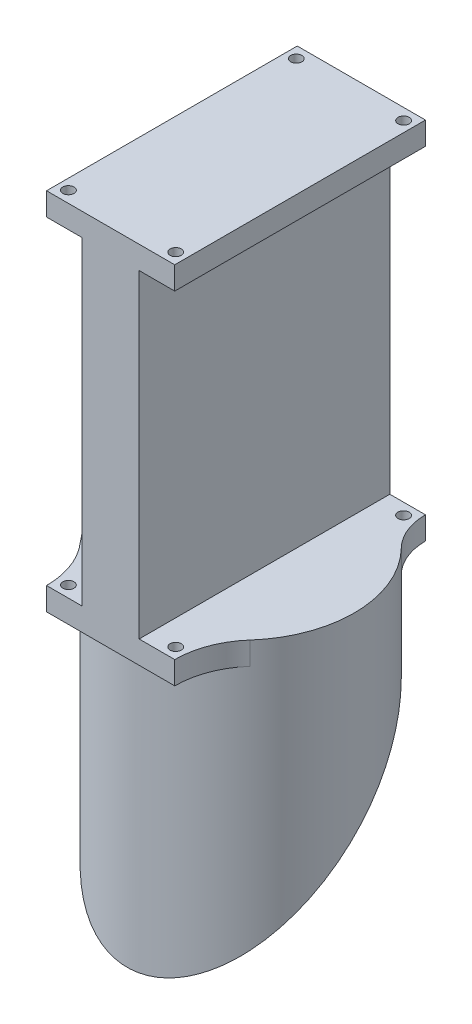
SolidWorks part; units mm, degrees
ref_plane "Front Plane" through (0, 0, 0) normal (0, 0, 1) x (1, 0, 0)
ref_plane "Top Plane" through (0, 0, 0) normal (0, 1, 0) x (1, 0, 0)
ref_plane "Right Plane" through (0, 0, 0) normal (1, 0, 0) x (0, 0, -1)
sketch "Sketch2" plane through (0, 0, 0) normal (1, 0, 0) x (0, 0, -1)
  line L0 (1.0414, 1055.2611) -> (1.0414, 991.9416) construction
  line L1 (1.0414, 1055.2611) -> (-24.2683, 1055.2611)
  line L2 (-24.2683, 1055.2611) -> (-24.2683, 991.9416)
  line L3 (-24.2683, 991.9416) -> (1.0414, 991.9416)
  line L4 (1.0414, 1055.2611) -> (1.0414, 991.9416)
revolve "Revolve1" add sketch "Sketch2" angle 360 about L0
sketch "Sketch3" plane through (0, 0, 0) normal (1, 0, 0) x (0, 0, -1)
  line L0 (-24.2683, 991.9416) -> (26.3511, 1042.5611)
  line L1 (26.3511, 1042.5611) -> (26.3511, 991.9416)
  line L2 (26.3511, 991.9416) -> (-24.2683, 991.9416)
extrude "Cut-Extrude1" cut sketch "Sketch3" against normal through all both and the other way through all
shell "Shell1" thickness 3.175 removed face at (0, 1042.5611, -26.3511)
sketch "Sketch4" plane through (0, 1055.2611, 0) normal (0, 1, 0) x (1, 0, 0)
  line L12 (14.2875, -27.94) -> (14.2875, 27.94) construction
  line L13 (14.2875, -27.94) -> (-14.2875, -27.94)
  line L14 (-14.2875, -27.94) -> (-14.2875, 27.94) construction
  line L15 (14.2875, 27.94) -> (-14.2875, 27.94)
  line L16 (14.2875, -27.94) -> (-14.2875, 27.94) construction
  line L17 (-14.2875, -27.94) -> (14.2875, 27.94) construction
  arc A0 (14.2875, 27.94) -> (18.0321, 18.8016) centre (27.3104, 27.94) ccw
  circle A1 centre (0, 1.0414) radius 25.3097
  arc A2 (-18.0321, 18.8016) -> (-18.9132, -15.7775) centre (0, 1.0414) ccw
  arc A3 (18.9132, -15.7775) -> (14.2875, -27.94) centre (32.5901, -27.94) ccw
  arc A4 (-14.2875, -27.94) -> (-18.9132, -15.7775) centre (-32.5901, -27.94) ccw
  arc A5 (-14.2875, 27.94) -> (-18.0321, 18.8016) centre (-27.3104, 27.94) cw
  arc A6 (18.9132, -15.7775) -> (18.0321, 18.8016) centre (0, 1.0414) ccw
  point P0 (0, 0)
  dimension "D1" = 28.575
  dimension "D2" = 55.88
  dimension "D3" = 0
extrude "Boss-Extrude1" add sketch "Sketch4" along normal blind 5.08
sketch "Sketch5" plane through (0, 1060.3411, 0) normal (0, 1, 0) x (1, 0, 0)
  line L1 (6.35, -27.94) -> (6.35, 27.94)
  line L2 (6.35, -27.94) -> (-6.35, -27.94)
  line L3 (-6.35, -27.94) -> (-6.35, 27.94)
  line L4 (6.35, 27.94) -> (-6.35, 27.94)
  line L5 (-6.35, 0) -> (6.35, 0) construction
  line L6 (0, -27.94) -> (0, 27.94) construction
  line L7 (14.2875, 27.94) -> (-14.2875, 27.94) construction
  point P0 (0, 0)
  dimension "D1" = 12.7
extrude "Boss-Extrude2" add sketch "Sketch5" along normal blind 76.2
sketch "Sketch10" plane through (0, 1136.5411, 0) normal (0, 1, 0) x (1, 0, 0)
  line L1 (-14.2875, 27.94) -> (14.2875, 27.94)
  line L2 (-14.2875, 27.94) -> (-14.2875, -27.94)
  line L3 (-14.2875, -27.94) -> (14.2875, -27.94)
  line L4 (14.2875, 27.94) -> (14.2875, -27.94)
extrude "Boss-Extrude3" add sketch "Sketch10" against normal blind 5.08
sketch "Sketch6" plane through (0, 1136.5411, 0) normal (0, 1, 0) x (1, 0, 0)
  line L0 (0, -22.225) -> (0, 22.225) construction
  point P4 (0, 0)
  dimension "D1" = 44.45
hole_wizard "M3x0.5 Tapped Hole1" positions "Sketch8" profile "Sketch9" tap size "M3x0.5" standard "ANSI Metric" end condition through all
sketch "Sketch8" plane through (0, 1136.5411, 0) normal (0, 1, 0) x (1, 0, 0)
  line L0 (-6.35, 27.94) -> (-14.2875, 27.94) construction
  line L1 (0, 0) -> (0, 27.94) construction
  line L2 (14.2875, 27.94) -> (-14.2875, 27.94) construction
  line L5 (0, 0) -> (25.2883, 0) construction
  arc A0 (-18.0321, 18.8016) -> (-14.2875, 27.94) centre (-27.3104, 27.94) ccw construction
  arc A1 (18.9132, -15.7775) -> (18.0321, 18.8016) centre (0, 1.0414) ccw construction
  point P0 (-11.9562, 25.4)
  point P2 (-11.9562, -25.4)
  point P4 (11.9562, -25.4)
  point P6 (11.9562, 25.4)
  point P34 (0, 0)
  point P35 (0, 0)
  point P36 (0, 0)
  point P37 (0, 0)
  point P38 (0, 0)
  dimension "D1" = 2.54
  dimension "D2" = 2.54
sketch "Sketch9" plane through (-11.9562, 1136.5411, -25.4) normal (1, 0, 0) x (0, 0, 1)
  line L0 (0, 0) -> (0, 144.5995)
  line L1 (0, 144.5995) -> (1.25, 144.5995)
  line L2 (1.25, 144.5995) -> (1.25, 0)
  line L5 (1.25, 0) -> (0, 0)
  line L11 (0, -6.35) -> (0, 107.95) construction
  dimension "Thru Tap Drill Dia." = 2.5
  dimension "Thru Tap Drill Depth" = 144.5995
cosmetic thread "Hole Thread13" parameters "D2"=3
cosmetic thread "Hole Thread14" parameters "D2"=3
cosmetic thread "Hole Thread15" parameters "D2"=3
cosmetic thread "Hole Thread16" parameters "D2"=3
sketch "Sketch7" plane through (0, 1055.2611, 0) normal (0, -1, 0) x (1, 0, 0)
  line L0 (0, 22.225) -> (0, -22.225) construction
  line L1 (0, 22.225) -> (0, -22.225) construction
